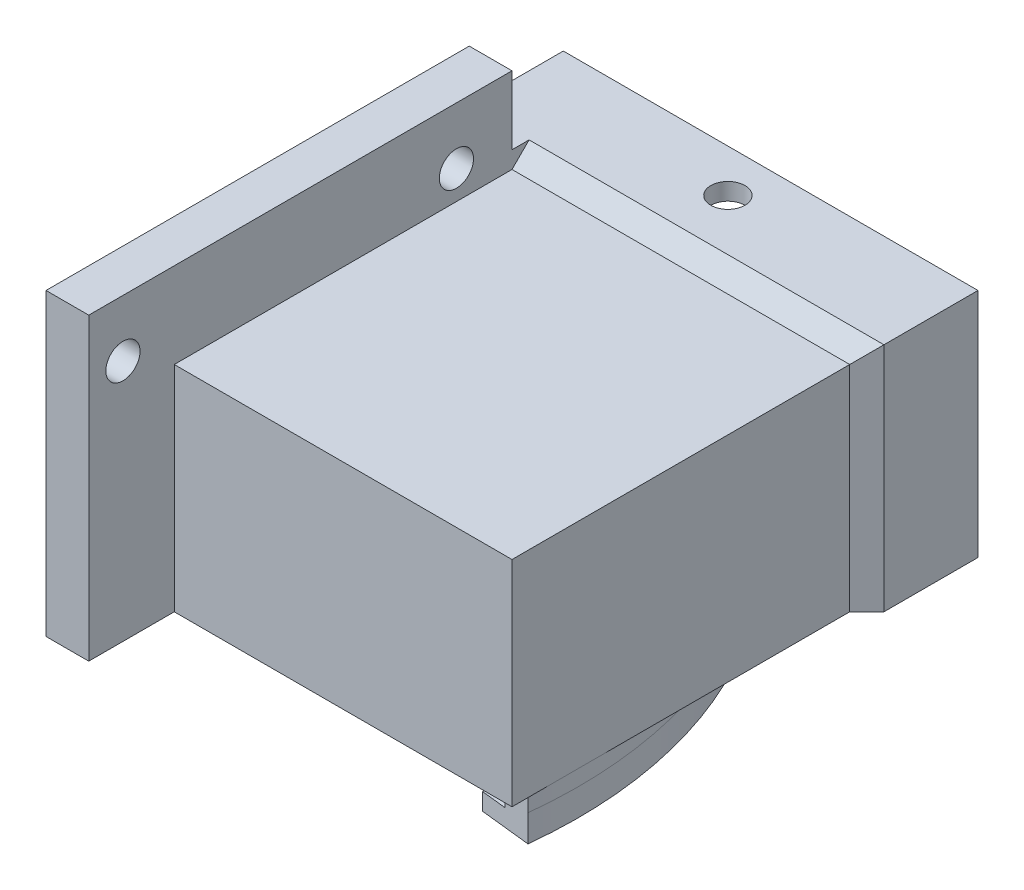
SolidWorks part; units mm, degrees
ref_plane "Płaszczyzna przednia" through (0, 0, 0) normal (0, 0, 1) x (1, 0, 0)
ref_plane "Płaszczyzna górna" through (0, 0, 0) normal (0, 1, 0) x (1, 0, 0)
ref_plane "Płaszczyzna prawa" through (0, 0, 0) normal (1, 0, 0) x (0, 0, -1)
sketch "Sketch1" plane through (0, 0, 0) normal (0, 0, 1) x (1, 0, 0)
  line L0 (-22.25, 11.525) -> (22.25, 11.525)
  line L1 (-19.95, 9.225) -> (19.95, 9.225)
  line L2 (-19.95, 9.225) -> (-19.95, -9.225)
  line L3 (-19.95, -9.225) -> (19.95, -9.225)
  line L4 (19.95, 9.225) -> (19.95, -9.225)
  line L5 (-19.95, 9.225) -> (19.95, -9.225) construction
  line L6 (-19.95, -9.225) -> (19.95, 9.225) construction
  line L7 (22.25, 11.525) -> (22.25, -11.525)
  line L8 (-22.25, -11.525) -> (22.25, -11.525)
  line L9 (-22.25, 11.525) -> (-22.25, -11.525)
  line L10 (-24.25, 13.525) -> (24.25, 13.525)
  line L11 (24.25, 13.525) -> (24.25, -13.525)
  line L12 (-24.25, -13.525) -> (24.25, -13.525)
  line L13 (-24.25, 13.525) -> (-24.25, -13.525)
  line L14 (22.25, -11.525) -> (22.25, -13.525)
  line L15 (-22.25, -11.525) -> (-22.25, -13.525)
  point P0 (0, 0)
  dimension "D1" = 39.9
  dimension "D2" = 18.45
  dimension "D5" = 23.05
  dimension "D6" = 44.5
  dimension "D3" = 2.3
  dimension "D4" = 2
extrude "Boss-Extrude1" add sketch "Sketch1" along normal blind 40 contours L8 L15 L12 L14 | L0 L7 L8 L9 | L1 L4 L3 L2 region at (0, -12.525, 0)
extrude "Boss-Extrude2" add sketch "Sketch1<3>" along normal blind 2.5 from surface contours L8 L15 L12 L14 | L0 L7 L8 L9 region at (0, -12.525, 0) starting at face at (0, -1, 40)
sketch "Sketch1<3>" plane through (0, 0, 0) normal (0, 0, 1) x (1, 0, 0) same geometry as "Sketch1"
extrude "Boss-Extrude3" add sketch "Sketch1<4>" along normal blind 3 and the other way blind 10 contours L10 L11 L12 L13 | L0 L7 L8 L9
sketch "Sketch1<4>" plane through (0, 0, 0) normal (0, 0, 1) x (1, 0, 0) same geometry as "Sketch1"
sketch "Sketch2" plane through (0, 0, 42.5) normal (0, 0, 1) x (1, 0, 0)
  line L1 (-22.25, 11.525) -> (-17.25, 11.525)
  line L2 (-22.25, 11.525) -> (-22.25, -13.525)
  line L3 (-22.25, -13.525) -> (-17.25, -13.525)
  line L4 (-17.25, 11.525) -> (-17.25, -13.525)
  line L5 (22.25, -13.525) -> (-22.25, -13.525) construction
  dimension "D1" = 5
extrude "Boss-Extrude4" add sketch "Sketch2" along normal blind 10
sketch "Sketch4" plane through (0, -13.525, 0) normal (0, -1, 0) x (1, 0, 0)
  line L0 (-14.5656, 40) -> (14.4424, 40)
  line L2 (-14.5656, 40) -> (-14.5656, 28.891)
  line L3 (-8.5656, 22.891) -> (13.124, 22.891)
  line L4 (20.2074, 34.6073) -> (20.2074, 34.5836)
  line L6 (22.25, 42.5) -> (22.25, 3) construction
  line L7 (22.25, 42.5) -> (-17.25, 42.5) construction
  arc A1 (13.124, 22.891) -> (14.4424, 40) centre (-29.1, 34.75) ccw
  arc A2 (1.0099, -3.0801) -> (18.9641, 40) centre (-29.1, 34.75) ccw
  arc A3 (21.2714, 24.7729) -> (22.1969, 37.0849) centre (-29.1, 34.75) ccw
  arc A4 (-14.5656, 28.891) -> (-8.5656, 22.891) centre (-8.5656, 28.891) ccw
  dimension "D2" = 2.5
  dimension "D1" = 3
  dimension "D3" = 6
ref_plane "Plane1" through (18.9641, -13.525, 40) normal (-0.1086, 0, 0.9941) x (0.9941, 0, 0.1086)
sketch "Sketch6" plane through (18.9641, -13.525, 40) normal (-0.1086, 0, 0.9941) x (0.9941, 0, 0.1086)
  line L0 (-999.9441, 0) -> (49000.0559, 0) construction
  line L1 (0, -1000.3743) -> (0, 48999.6257) construction
  line L2 (-0.0072, -3) -> (-3.0072, -3)
  line L3 (-0.0072, 0) -> (2.9928, 0)
  line L4 (-0.0072, 0) -> (-0.0072, -3)
  line L6 (2.9928, 0) -> (2.9928, -1.8481)
  line L8 (2.9928, -1.8481) -> (2.9928, -5)
  line L9 (2.9928, -5) -> (-3.0072, -5)
  line L10 (-3.0072, -3) -> (-3.0072, -5)
  dimension "D1" = 3
  dimension "D2" = 3
  dimension "D3" = 6
  dimension "D4" = 5
sweep "Sweep1" add profiles "Sketch6" path "Sketch4"
extrude "Cut-Extrude1" cut sketch "Sketch4<3>" against normal up to next contours L3 A1 L0 L2 region at (0.1044, -13.525, 31.6254)
sketch "Sketch4<3>" plane through (0, -13.525, 0) normal (0, -1, 0) x (1, 0, 0) same geometry as "Sketch4"
sketch "Sketch7" plane through (0, 11.525, 0) normal (0, 1, 0) x (1, 0, 0)
  line L0 (-17.25, -52.5) -> (-17.25, -42.5) construction
  line L1 (-22.25, -52.5) -> (-17.25, -52.5)
  line L2 (-22.25, -52.5) -> (-22.25, -3)
  line L3 (-22.25, -3) -> (-17.25, -3)
  line L4 (-17.25, -52.5) -> (-17.25, -3)
  line L5 (-24.25, -3) -> (24.25, -3) construction
extrude "Boss-Extrude5" add sketch "Sketch7" along normal blind 10
sketch "Sketch8" plane through (-22.25, 0, 0) normal (-1, 0, 0) x (0, 0, 1)
  circle A0 centre (48.5, 14.875) radius 2
  circle A1 centre (9.5, 14.875) radius 2
  dimension "D1" = 4
extrude "Cut-Extrude2" cut sketch "Sketch8" against normal blind 5.8
chamfer "Chamfer1" distance 2 angle 45 1 edges at (3.5, 13.525, 3)
chamfer "Chamfer2" distance 2 angle 45 1 edges at (24.25, -1, 3)
sketch "Sketch9" plane through (0, 13.525, 0) normal (0, 1, 0) x (1, 0, 0)
  line L0 (0, 10) -> (0, 0) construction
  line L1 (-24.25, 10) -> (24.25, 10) construction
  circle A0 centre (0, 5) radius 2
  dimension "D1" = 4
extrude "Cut-Extrude3" cut sketch "Sketch9" against normal blind 10
